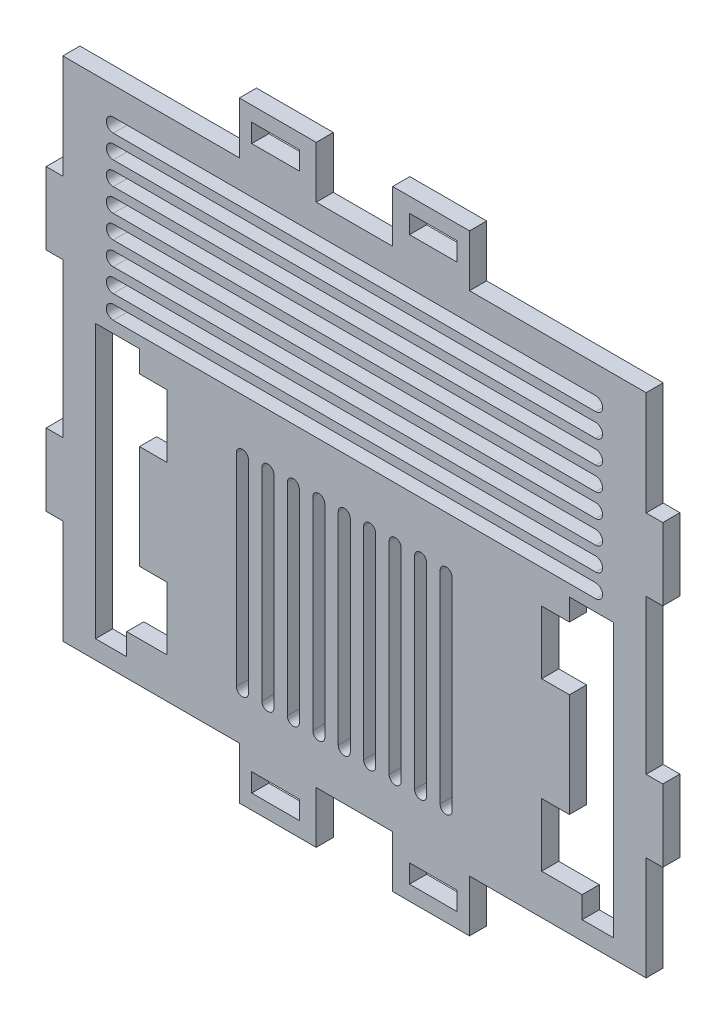
SolidWorks part; units mm, degrees
ref_plane "Front Plane" through (0, 0, 0) normal (0, 0, 1) x (1, 0, 0)
ref_plane "Top Plane" through (0, 0, 0) normal (0, 1, 0) x (1, 0, 0)
ref_plane "Right Plane" through (0, 0, 0) normal (1, 0, 0) x (0, 0, -1)
sketch "Sketch1" plane through (0, 0, 0) normal (0, 0, 1) x (1, 0, 0)
  line L0 (0, 83.1516) -> (0, -85.2047) construction
  line L1 (63, -54.75) -> (24.86, -54.75)
  line L2 (63, -54.75) -> (63, -32.25)
  line L3 (63, 54.75) -> (24.86, 54.75)
  line L4 (-63, -54.75) -> (-63, -32.25)
  line L5 (63, -54.75) -> (-63, 54.75) construction
  line L6 (63, 54.75) -> (-63, -54.75) construction
  line L10 (-87.1896, 0) -> (78.4288, 0) construction
  line L20 (-24.86, 54.75) -> (-63, 54.75)
  line L21 (8.26, 54.75) -> (-8.26, 54.75)
  line L22 (-24.86, -54.75) -> (-63, -54.75)
  line L23 (8.26, -54.75) -> (-8.26, -54.75)
  line L24 (63, 32.25) -> (66.6, 32.25)
  line L25 (66.6, 32.25) -> (66.6, 16.65)
  line L26 (66.6, 16.65) -> (63, 16.65)
  line L27 (66.6, -16.65) -> (63, -16.65)
  line L28 (63, -32.25) -> (66.6, -32.25)
  line L29 (66.6, -32.25) -> (66.6, -16.65)
  line L30 (-66.6, -32.25) -> (-66.6, -16.65)
  line L31 (-63, -32.25) -> (-66.6, -32.25)
  line L32 (-66.6, -16.65) -> (-63, -16.65)
  line L33 (-66.6, 16.65) -> (-63, 16.65)
  line L34 (-66.6, 32.25) -> (-66.6, 16.65)
  line L35 (-63, 32.25) -> (-66.6, 32.25)
  line L36 (-63, 32.25) -> (-63, 54.75)
  line L37 (-63, -16.65) -> (-63, 16.65)
  line L38 (63, -16.65) -> (63, 16.65)
  line L39 (63, 32.25) -> (63, 54.75)
  line L44 (-24.86, 65.95) -> (-24.86, 54.75)
  line L45 (-24.86, 65.95) -> (-8.26, 65.95)
  line L46 (-8.26, 65.95) -> (-8.26, 54.75)
  line L47 (8.26, 65.95) -> (8.26, 54.75)
  line L48 (-11.8923, 58.75) -> (-22.1923, 58.75)
  line L49 (-11.8923, 58.75) -> (-11.8923, 62.75)
  line L50 (-11.8923, 62.75) -> (-22.1923, 62.75)
  line L51 (-22.1923, 58.75) -> (-22.1923, 62.75)
  line L52 (-11.8923, 58.75) -> (-22.1923, 62.75) construction
  line L53 (-11.8923, 62.75) -> (-22.1923, 58.75) construction
  line L54 (24.86, 65.95) -> (24.86, 54.75)
  line L55 (11.8923, 62.75) -> (22.1923, 58.75) construction
  line L56 (11.8923, 58.75) -> (22.1923, 62.75) construction
  line L57 (22.1923, 58.75) -> (22.1923, 62.75)
  line L58 (11.8923, 62.75) -> (22.1923, 62.75)
  line L59 (11.8923, 58.75) -> (11.8923, 62.75)
  line L60 (11.8923, 58.75) -> (22.1923, 58.75)
  line L61 (24.86, 65.95) -> (8.26, 65.95)
  line L62 (11.8923, -58.75) -> (22.1923, -62.75) construction
  line L63 (11.8923, -62.75) -> (22.1923, -58.75) construction
  line L64 (11.8923, -58.75) -> (22.1923, -58.75)
  line L65 (11.8923, -58.75) -> (11.8923, -62.75)
  line L66 (11.8923, -62.75) -> (22.1923, -62.75)
  line L67 (22.1923, -58.75) -> (22.1923, -62.75)
  line L68 (24.86, -65.95) -> (24.86, -54.75)
  line L69 (24.86, -65.95) -> (8.26, -65.95)
  line L70 (8.26, -65.95) -> (8.26, -54.75)
  line L71 (-8.26, -65.95) -> (-8.26, -54.75)
  line L72 (-24.86, -65.95) -> (-24.86, -54.75)
  line L73 (-11.8923, -62.75) -> (-22.1923, -58.75) construction
  line L74 (-11.8923, -58.75) -> (-22.1923, -62.75) construction
  line L75 (-22.1923, -58.75) -> (-22.1923, -62.75)
  line L76 (-11.8923, -62.75) -> (-22.1923, -62.75)
  line L77 (-11.8923, -58.75) -> (-11.8923, -62.75)
  line L78 (-11.8923, -58.75) -> (-22.1923, -58.75)
  line L79 (-24.86, -65.95) -> (-8.26, -65.95)
  point P0 (0, 0)
  point P10 (-17.0423, 60.75)
  point P47 (17.0423, 60.75)
  point P52 (17.0423, -60.75)
  point P61 (-17.0423, -60.75)
  dimension "D1" = 109.5
  dimension "D2" = 126
  dimension "D3" = 16.6
  dimension "D4" = 11.2
  dimension "D5" = 38.14
  dimension "D6" = 15.6
  dimension "D7" = 3.6
  dimension "D8" = 22.5
  dimension "D9" = 10.3
  dimension "D10" = 4
  dimension "D11" = 3.2
extrude "Boss-Extrude1" add sketch "Sketch1" along normal blind 3.7
sketch "Sketch2" plane through (0, 0, 3.7) normal (0, 0, 1) x (1, 0, 0)
  line L0 (0, 54.75) -> (0, -54.75) construction
  line L1 (8.26, 54.75) -> (-8.26, 54.75) construction
  line L2 (-8.26, -54.75) -> (8.26, -54.75) construction
  line L3 (-63, 0) -> (63, 0) construction
  line L4 (-63, 16.65) -> (-63, -16.65) construction
  line L5 (63, -16.65) -> (63, 16.65) construction
  line L6 (52.1, 47.25) -> (-52.1, 47.25) construction
  line L7 (52.1, 45.75) -> (-52.1, 45.75)
  line L8 (52.1, 48.75) -> (-52.1, 48.75)
  line L9 (-24.86, 54.75) -> (-63, 54.75) construction
  line L12 (52.1, 42.25) -> (-52.1, 42.25) construction
  line L13 (52.1, 40.75) -> (-52.1, 40.75)
  line L14 (52.1, 43.75) -> (-52.1, 43.75)
  line L15 (52.1, 37.25) -> (-52.1, 37.25) construction
  line L16 (52.1, 35.75) -> (-52.1, 35.75)
  line L17 (52.1, 38.75) -> (-52.1, 38.75)
  line L18 (52.1, 32.25) -> (-52.1, 32.25) construction
  line L19 (52.1, 30.75) -> (-52.1, 30.75)
  line L20 (52.1, 33.75) -> (-52.1, 33.75)
  line L21 (52.1, 27.25) -> (-52.1, 27.25) construction
  line L22 (52.1, 25.75) -> (-52.1, 25.75)
  line L23 (52.1, 28.75) -> (-52.1, 28.75)
  line L24 (52.1, 22.25) -> (-52.1, 22.25) construction
  line L25 (52.1, 20.75) -> (-52.1, 20.75)
  line L26 (52.1, 23.75) -> (-52.1, 23.75)
  line L27 (52.1, 17.25) -> (-52.1, 17.25) construction
  line L28 (52.1, 15.75) -> (-52.1, 15.75)
  line L29 (52.1, 18.75) -> (-52.1, 18.75)
  line L30 (52.1, 12.25) -> (-52.1, 12.25) construction
  line L31 (52.1, 10.75) -> (-52.1, 10.75)
  line L32 (52.1, 13.75) -> (-52.1, 13.75)
  line L33 (-24.2, -44.45) -> (-24.2, -0.75) construction
  line L34 (-25.5, -44.45) -> (-25.5, -0.75)
  line L35 (-22.9, -44.45) -> (-22.9, -0.75)
  line L36 (-63, -54.75) -> (-24.86, -54.75) construction
  line L37 (-63, -32.25) -> (-63, -54.75) construction
  line L38 (-18.7, -44.45) -> (-18.7, -0.75) construction
  line L39 (-20, -44.45) -> (-20, -0.75)
  line L40 (-17.4, -44.45) -> (-17.4, -0.75)
  line L41 (-13.2, -44.45) -> (-13.2, -0.75) construction
  line L42 (-14.5, -44.45) -> (-14.5, -0.75)
  line L43 (-11.9, -44.45) -> (-11.9, -0.75)
  line L44 (-7.7, -44.45) -> (-7.7, -0.75) construction
  line L45 (-9, -44.45) -> (-9, -0.75)
  line L46 (-6.4, -44.45) -> (-6.4, -0.75)
  line L47 (-2.2, -44.45) -> (-2.2, -0.75) construction
  line L48 (-3.5, -44.45) -> (-3.5, -0.75)
  line L49 (-0.9, -44.45) -> (-0.9, -0.75)
  line L50 (3.3, -44.45) -> (3.3, -0.75) construction
  line L51 (2, -44.45) -> (2, -0.75)
  line L52 (4.6, -44.45) -> (4.6, -0.75)
  line L53 (8.8, -44.45) -> (8.8, -0.75) construction
  line L54 (7.5, -44.45) -> (7.5, -0.75)
  line L55 (10.1, -44.45) -> (10.1, -0.75)
  line L56 (14.3, -44.45) -> (14.3, -0.75) construction
  line L57 (13, -44.45) -> (13, -0.75)
  line L58 (15.6, -44.45) -> (15.6, -0.75)
  line L59 (19.8, -44.45) -> (19.8, -0.75) construction
  line L60 (18.5, -44.45) -> (18.5, -0.75)
  line L61 (21.1, -44.45) -> (21.1, -0.75)
  arc A0 (52.1, 45.75) -> (52.1, 48.75) centre (52.1, 47.25) ccw
  arc A1 (-52.1, 48.75) -> (-52.1, 45.75) centre (-52.1, 47.25) ccw
  arc A2 (52.1, 40.75) -> (52.1, 43.75) centre (52.1, 42.25) ccw
  arc A3 (-52.1, 43.75) -> (-52.1, 40.75) centre (-52.1, 42.25) ccw
  arc A4 (52.1, 35.75) -> (52.1, 38.75) centre (52.1, 37.25) ccw
  arc A5 (-52.1, 38.75) -> (-52.1, 35.75) centre (-52.1, 37.25) ccw
  arc A6 (52.1, 30.75) -> (52.1, 33.75) centre (52.1, 32.25) ccw
  arc A7 (-52.1, 33.75) -> (-52.1, 30.75) centre (-52.1, 32.25) ccw
  arc A8 (52.1, 25.75) -> (52.1, 28.75) centre (52.1, 27.25) ccw
  arc A9 (-52.1, 28.75) -> (-52.1, 25.75) centre (-52.1, 27.25) ccw
  arc A10 (52.1, 20.75) -> (52.1, 23.75) centre (52.1, 22.25) ccw
  arc A11 (-52.1, 23.75) -> (-52.1, 20.75) centre (-52.1, 22.25) ccw
  arc A12 (52.1, 15.75) -> (52.1, 18.75) centre (52.1, 17.25) ccw
  arc A13 (-52.1, 18.75) -> (-52.1, 15.75) centre (-52.1, 17.25) ccw
  arc A14 (52.1, 10.75) -> (52.1, 13.75) centre (52.1, 12.25) ccw
  arc A15 (-52.1, 13.75) -> (-52.1, 10.75) centre (-52.1, 12.25) ccw
  arc A16 (-25.5, -44.45) -> (-22.9, -44.45) centre (-24.2, -44.45) ccw
  arc A17 (-22.9, -0.75) -> (-25.5, -0.75) centre (-24.2, -0.75) ccw
  arc A18 (-20, -44.45) -> (-17.4, -44.45) centre (-18.7, -44.45) ccw
  arc A19 (-17.4, -0.75) -> (-20, -0.75) centre (-18.7, -0.75) ccw
  arc A20 (-14.5, -44.45) -> (-11.9, -44.45) centre (-13.2, -44.45) ccw
  arc A21 (-11.9, -0.75) -> (-14.5, -0.75) centre (-13.2, -0.75) ccw
  arc A22 (-9, -44.45) -> (-6.4, -44.45) centre (-7.7, -44.45) ccw
  arc A23 (-6.4, -0.75) -> (-9, -0.75) centre (-7.7, -0.75) ccw
  arc A24 (-3.5, -44.45) -> (-0.9, -44.45) centre (-2.2, -44.45) ccw
  arc A25 (-0.9, -0.75) -> (-3.5, -0.75) centre (-2.2, -0.75) ccw
  arc A26 (2, -44.45) -> (4.6, -44.45) centre (3.3, -44.45) ccw
  arc A27 (4.6, -0.75) -> (2, -0.75) centre (3.3, -0.75) ccw
  arc A28 (7.5, -44.45) -> (10.1, -44.45) centre (8.8, -44.45) ccw
  arc A29 (10.1, -0.75) -> (7.5, -0.75) centre (8.8, -0.75) ccw
  arc A30 (13, -44.45) -> (15.6, -44.45) centre (14.3, -44.45) ccw
  arc A31 (15.6, -0.75) -> (13, -0.75) centre (14.3, -0.75) ccw
  arc A32 (18.5, -44.45) -> (21.1, -44.45) centre (19.8, -44.45) ccw
  arc A33 (21.1, -0.75) -> (18.5, -0.75) centre (19.8, -0.75) ccw
  point P14 (0, 47.25)
  point P19 (-50.6, 47.25)
  point P20 (50.6, 47.25)
  point P25 (-24.2, -22.6)
  point P30 (0, 42.25)
  point P37 (0, 37.25)
  point P44 (0, 32.25)
  point P51 (0, 27.25)
  point P58 (0, 22.25)
  point P65 (0, 17.25)
  point P72 (0, 12.25)
  point P79 (-24.2, -45.75)
  point P82 (-24.2, 0.55)
  point P85 (0, 0)
  point P88 (-18.7, -22.6)
  point P95 (-13.2, -22.6)
  point P102 (-7.7, -22.6)
  point P109 (-2.2, -22.6)
  point P116 (3.3, -22.6)
  point P123 (8.8, -22.6)
  point P130 (14.3, -22.6)
  point P137 (19.8, -22.6)
  point P142 (0, 0)
  point P143 (0, 0)
  dimension "D1" = 101.2
  dimension "D2" = 3
  dimension "D3" = 6
  dimension "D4" = 8
  dimension "D5" = 9
  dimension "D6" = 2.6
  dimension "D7" = 46.3
  dimension "D8" = 37.5
  dimension "D10" = 2
  dimension "D9" = 9
extrude "Cut-Extrude2" cut sketch "Sketch2" against normal through all contours L7 A1 L8 A0
extrude "Cut-Extrude3" cut sketch "Sketch2<3>" against normal through all
sketch "Sketch2<3>" plane through (0, 0, 3.7) normal (0, 0, 1) x (1, 0, 0) same geometry as "Sketch2"
sketch "Sketch4" plane through (0, 0, 3.7) normal (0, 0, 1) x (1, 0, 0)
  line L0 (-55.936, 8.25) -> (-55.936, -50.75)
  line L1 (-55.936, -50.75) -> (-49.192, -50.75)
  line L2 (-49.192, -50.75) -> (-49.192, -46.05)
  line L3 (-49.192, -46.05) -> (-40.436, -46.05)
  line L4 (-40.436, -46.05) -> (-40.436, -32.45)
  line L5 (-40.436, -32.45) -> (-46.436, -32.45)
  line L6 (-46.436, -32.45) -> (-46.436, -10.05)
  line L7 (-46.436, -10.05) -> (-40.436, -10.05)
  line L8 (-40.436, -10.05) -> (-40.436, 3.55)
  line L9 (-40.436, 3.55) -> (-46.436, 3.55)
  line L10 (-46.436, 3.55) -> (-46.436, 8.25)
  line L11 (-46.436, 8.25) -> (-55.936, 8.25)
  line L12 (-63, -54.75) -> (-24.86, -54.75) construction
  line L14 (0, 54.75) -> (0, -54.75) construction
  line L15 (46.436, 3.55) -> (46.436, 8.25)
  line L16 (40.436, 3.55) -> (46.436, 3.55)
  line L17 (40.436, -10.05) -> (40.436, 3.55)
  line L18 (46.436, -10.05) -> (40.436, -10.05)
  line L19 (46.436, -32.45) -> (46.436, -10.05)
  line L20 (40.436, -32.45) -> (46.436, -32.45)
  line L21 (40.436, -46.05) -> (40.436, -32.45)
  line L22 (49.192, -46.05) -> (40.436, -46.05)
  line L23 (49.192, -50.75) -> (49.192, -46.05)
  line L24 (55.936, -50.75) -> (49.192, -50.75)
  line L25 (55.936, 8.25) -> (55.936, -50.75)
  line L26 (46.436, 8.25) -> (55.936, 8.25)
  dimension "D1" = 59
  dimension "D2" = 4
  dimension "D3" = 4.7
  dimension "D4" = 13.6
  dimension "D5" = 9.5
  dimension "D6" = 9.5
  dimension "D7" = 6
  dimension "D8" = 6
extrude "Cut-Extrude4" cut sketch "Sketch4" against normal through all
